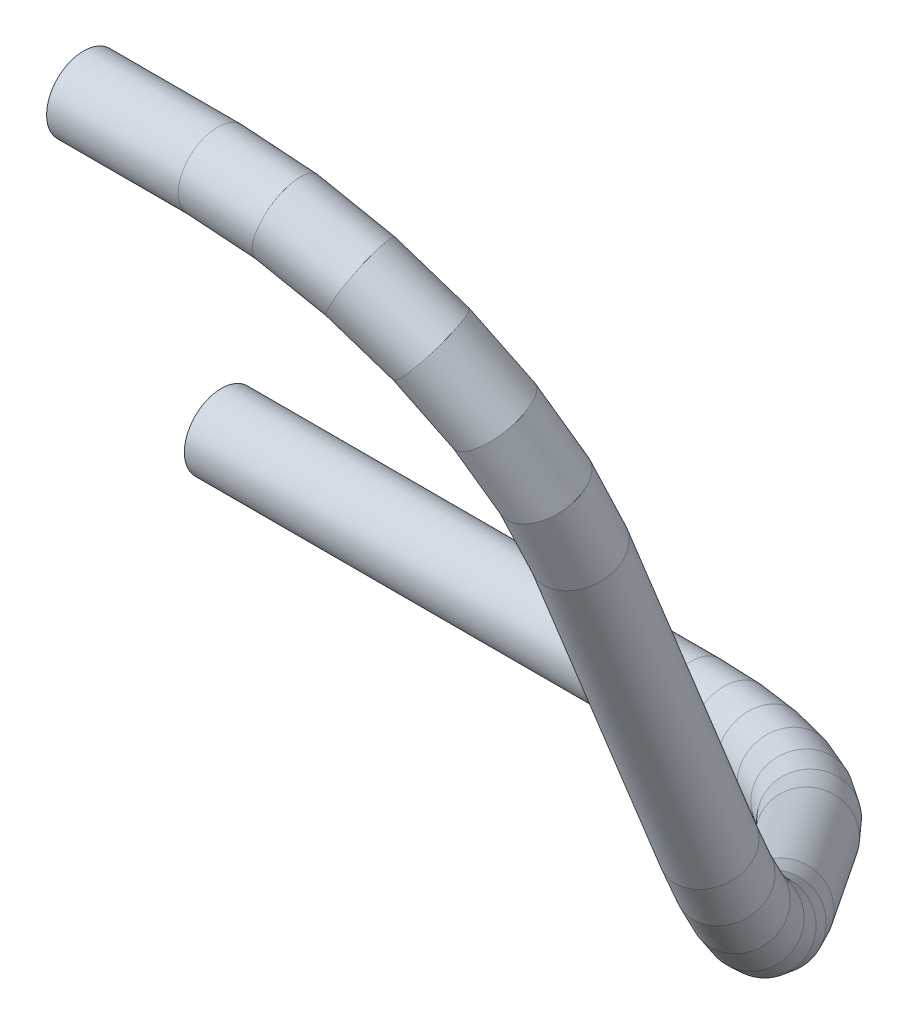
SolidWorks part; units mm, degrees
ref_plane "Front Plane" through (0, 0, 0) normal (0, 0, 1) x (1, 0, 0)
ref_plane "Top Plane" through (0, 0, 0) normal (0, 1, 0) x (1, 0, 0)
ref_plane "Right Plane" through (0, 0, 0) normal (1, 0, 0) x (0, 0, -1)
sketch3d "Path"
  line L0 (-571, -44.8888, -108.3711) -> (-539.0671, -44.8888, -108.3711)
  line L1 (-539.0671, -44.8888, -108.3711) -> (-536.2786, -44.8056, -108.1703)
  line L2 (-536.2786, -44.8056, -108.1703) -> (-533.5575, -44.5581, -107.5729)
  line L3 (-533.5575, -44.5581, -107.5729) -> (-530.9693, -44.1524, -106.5932)
  line L4 (-530.9693, -44.1524, -106.5932) -> (-528.5767, -43.598, -105.2549)
  line L5 (-528.5767, -43.598, -105.2549) -> (-526.4374, -42.9086, -103.5904)
  line L6 (-526.4374, -42.9086, -103.5904) -> (-524.603, -42.1006, -101.6398)
  line L7 (-524.603, -42.1006, -101.6398) -> (-517.6708, -38.5192, -92.9936)
  line L8 (-517.6708, -38.5192, -92.9936) -> (-516.0356, -37.4091, -90.8474)
  line L9 (-516.0356, -37.4091, -90.8474) -> (-514.6348, -35.8965, -88.7829)
  line L10 (-514.6348, -35.8965, -88.7829) -> (-513.5051, -34.0212, -86.8544)
  line L11 (-513.5051, -34.0212, -86.8544) -> (-512.6763, -31.8323, -85.1126)
  line L12 (-512.6763, -31.8323, -85.1126) -> (-512.1702, -29.3873, -83.6031)
  line L13 (-512.1702, -29.3873, -83.6031) -> (-512, -26.7507, -82.3656)
  line L14 (-512, -26.7507, -82.3656) -> (-512, -4.9998, -73.617)
  line L15 (-512, -4.9998, -73.617) -> (-512.6133, -0.6775, -71.8785)
  line L16 (-512.6133, -0.6775, -71.8785) -> (-514.4115, 3.3501, -70.2585)
  line L17 (-514.4115, 3.3501, -70.2585) -> (-517.2721, 6.8088, -68.8674)
  line L18 (-517.2721, 6.8088, -68.8674) -> (-521, 9.4627, -67.7999)
  line L19 (-521, 9.4627, -67.7999) -> (-525.3413, 11.131, -67.1289)
  line L20 (-525.3413, 11.131, -67.1289) -> (-530, 11.7, -66.9)
  line L21 (-530, 11.7, -66.9) -> (-538.85, 11.7, -66.9)
ref_plane "Start Plane" through (-571, 0, 0) normal (1, 0, 0) x (0, 0, -1)
sketch "Profile" plane through (-571, 0, 0) normal (1, 0, 0) x (0, 0, -1)
  circle A0 centre (108.3711, -44.8888) radius 2.5
  circle A1 centre (108.3711, -44.8888) radius 1
sweep "Tube" add profiles "Profile" path "Path"
ref_axis "Engine Axis" through (-506.425, 0, 0) along (-1, 0, 0)
